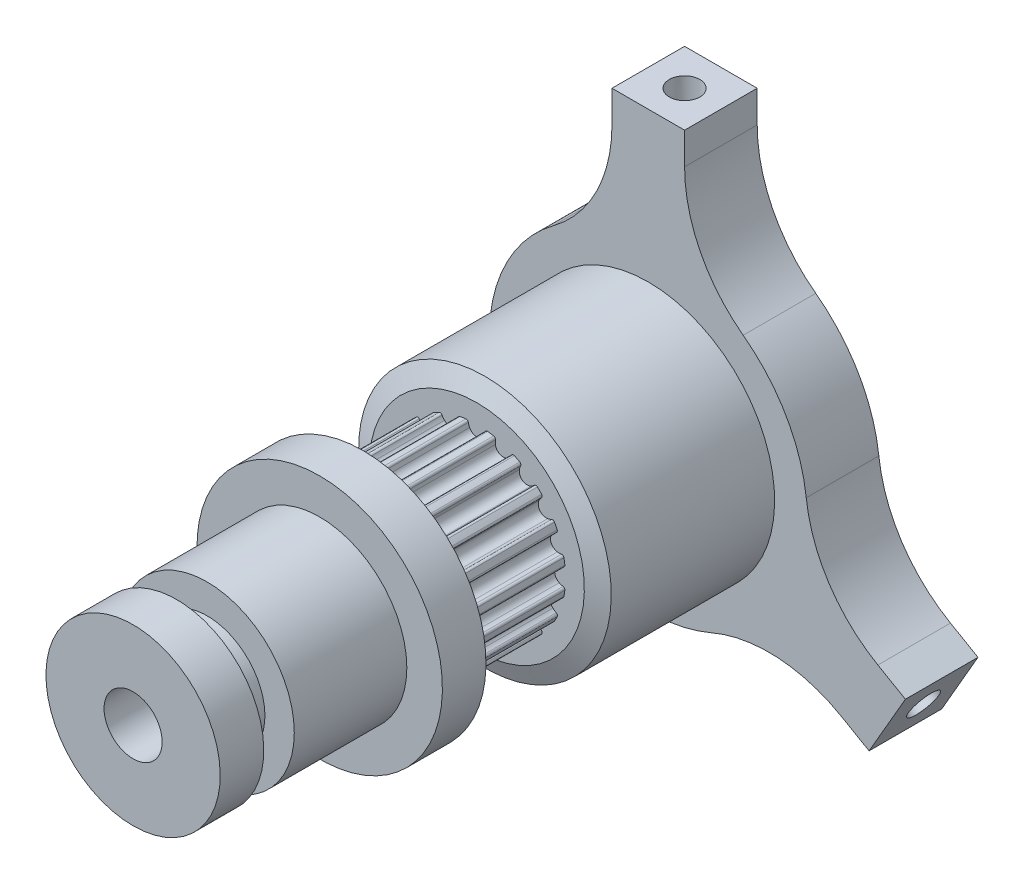
SolidWorks part; units mm, degrees
ref_plane "Front Plane" through (0, 0, 0) normal (0, 0, 1) x (1, 0, 0)
ref_plane "Top Plane" through (0, 0, 0) normal (0, 1, 0) x (1, 0, 0)
ref_plane "Right Plane" through (0, 0, 0) normal (1, 0, 0) x (0, 0, -1)
sketch "Sketch10" plane through (0, 0, 0) normal (0, 0, 1) x (1, 0, 0)
  circle A0 centre (0, 0) radius 2 construction
  dimension "D1" = 4
sketch "Sketch1" plane through (0, 0, 0) normal (0, 0, 1) x (1, 0, 0)
  line L5 (7.9825, -7.4955) -> (15.2045, -11.6651)
  line L6 (10.4825, -3.1653) -> (17.7045, -7.3349)
  line L7 (15.2045, -11.6651) -> (17.7045, -7.3349)
  line L9 (-10.4825, -3.1653) -> (-17.7045, -7.3349)
  line L10 (-7.9825, -7.4955) -> (-15.2045, -11.6651)
  line L11 (-17.7045, -7.3349) -> (-15.2045, -11.6651)
  line L13 (-2.5, 10.6608) -> (-2.5, 19)
  line L14 (2.5, 10.6608) -> (2.5, 19)
  line L15 (-2.5, 19) -> (2.5, 19)
  line L16 (-10.4825, -3.1653) -> (-2.5, 10.6608) construction
  line L17 (2.5, 10.6608) -> (10.4825, -3.1653) construction
  line L18 (-7.9825, -7.4955) -> (7.9825, -7.4955) construction
  line L19 (2.5, 19) -> (17.7045, -7.3349) construction
  line L20 (15.2045, -11.6651) -> (-15.2045, -11.6651) construction
  line L21 (-17.7045, -7.3349) -> (-2.5, 19) construction
  arc A0 (10.4825, -3.1653) -> (2.5, 10.6608) centre (0, 0) ccw
  arc A1 (-2.5, 10.6608) -> (-10.4825, -3.1653) centre (0, 0) ccw
  arc A2 (-7.9825, -7.4955) -> (7.9825, -7.4955) centre (0, 0) ccw
  dimension "D1" = 21.9
  dimension "D2" = 5
  dimension "D3" = 19
extrude "Boss-Extrude1" add sketch "Sketch1" along normal blind 5
sketch "main_revolve_sketch" plane through (0, 0, 0) normal (1, 0, 0) x (0, 0, -1)
  line L0 (-5, 0) -> (-5, 8.7)
  line L1 (-5, 8.7) -> (-16.25, 8.7)
  line L2 (-16.25, 8.7) -> (-16.8068, 7.404)
  line L3 (-16.8068, 7.404) -> (-16.8068, 6.1085)
  line L4 (-16.8068, 6.1085) -> (-24.1768, 6.1085)
  line L5 (-24.1768, 6.1085) -> (-24.1768, 7.404)
  line L6 (-24.1768, 7.404) -> (-24.6263, 8.45)
  line L7 (-24.6263, 8.45) -> (-27.6263, 8.45)
  line L8 (-5, 0) -> (-27.6263, 0) construction
  line L9 (-27.6263, 8.45) -> (-27.6263, 0)
  line L10 (-24.1768, 7.404) -> (-24.7337, 8.7) construction
  line L11 (-20.4918, 6.1085) -> (-20.4918, 0) construction
  line L12 (-5, 10.6608) -> (-5, -3.1653) construction
  line L13 (-5, 0) -> (-27.6263, 0)
  line L14 (-24.7337, 8.7) -> (-16.25, 8.7) construction
  line L15 (-20.4918, 8.7) -> (-20.4918, 6.1085) construction
  dimension "D1" = 17.4
  dimension "D2" = 7.37
  dimension "D3" = 8.38
  dimension "D4" = 12.217
  dimension "D5" = 14.808
  dimension "length_difference" = 11.25
  dimension "D7" = 3
  dimension "D8" = 0.25
revolve "main_revolve" add sketch "main_revolve_sketch" angle 360 about L13
sketch "Sketch11" plane through (0, 0, 27.6263) normal (0, 0, 1) x (1, 0, 0)
  circle A2 centre (0, 0) radius 6
  circle A3 centre (0, 0) radius 6
  dimension "D1" = 4
extrude "Boss-Extrude3" add sketch "Sketch11" along normal blind 7.75
sketch "Sketch13" plane through (0, 0, 0) normal (1, 0, 0) x (0, 0, -1)
  line L0 (-35.3763, 0) -> (-35.3763, 3.9775)
  line L1 (-35.3763, 6) -> (-35.3763, -6) construction
  line L2 (-35.3763, 3.9775) -> (-37.4763, 3.9775)
  line L3 (-37.4763, 3.9775) -> (-37.4763, 6)
  line L4 (-37.4763, 6) -> (-40.4763, 6)
  line L5 (-40.4763, 6) -> (-40.4763, 0)
  line L6 (-40.4763, 0) -> (-35.3763, 0) construction
  line L7 (-27.6263, 6) -> (-35.3763, 6) construction
  line L8 (-35.3763, 0) -> (-40.4763, 0)
  dimension "D1" = 3
  dimension "D2" = 2.1
  dimension "D3" = 7.955
revolve "Revolve2" add sketch "Sketch13" angle 360 about L6
sketch "Sketch2" plane through (0, 19, 0) normal (0, 1, 0) x (1, 0, 0)
  line L0 (0, 0) -> (0, -2.5) construction
  line L1 (0, -2.5) -> (2.5, -2.5) construction
  line L2 (2.5, -5) -> (2.5, 0) construction
  circle A0 centre (0, -2.5) radius 1.05
  dimension "D1" = 2.1
extrude "Cut-Extrude1" cut sketch "Sketch2" against normal blind 10
pattern_circular "CirPattern2" count 3 over 360 about axis through (0, 0, 5) along (0, 0, -1) of "Cut-Extrude1"
draft "Draft4" type of draft neutral plane draft angle 1 faces to draft 1 face at (0, 9, 3.55) neutral plane through (-2.5, 19, 5) neutral plane normal (0, 1, 0) parameters "D1"=1
draft "Draft5" type of draft neutral plane draft angle 1 faces to draft 1 face at (-7.7942, -4.5, 3.55) neutral plane through (-17.7045, -7.3349, 5) neutral plane normal (-0.866, -0.5, 0) parameters "D1"=1
draft "Draft6" type of draft neutral plane draft angle 1 faces to draft 1 face at (7.7942, -4.5, 3.55) neutral plane through (15.2045, -11.6651, 5) neutral plane normal (0.866, -0.5, 0) parameters "D1"=1
sketch "Sketch3" plane through (0, 0, 0) normal (0, 0, -1) x (-1, 0, 0)
  circle A0 centre (0, 0) radius 2
  circle A1 centre (0, 0) radius 2 construction
extrude "Cut-Extrude2" cut sketch "Sketch3" against normal through all
sketch "Sketch7" plane through (0, 0, 16.8068) normal (0, 0, 1) x (1, 0, 0)
  line B0 (0, 0) -> (0, 5.3585) construction
  line B1 (-1.8963, 5.8067) -> (-2.841, 8.6995)
  line B2 (-2.841, 8.6995) -> (2.841, 8.6995)
  line B3 (2.841, 8.6995) -> (1.8963, 5.8067)
  arc B4 (-0.4989, 5.6703) -> (0.4989, 5.6703) centre (0, 5.9135) ccw
  arc B5 (-0.4989, 5.6703) -> (-0.5855, 5.9387) centre (0.4, 6.1085) cw
  arc B6 (-1.8963, 5.8067) -> (-0.7518, 6.0621) centre (0, 0) cw
  arc B7 (-0.5855, 5.9387) -> (-0.7518, 6.0621) centre (-0.7333, 5.9132) ccw
  arc B8 (1.8963, 5.8067) -> (0.7518, 6.0621) centre (0, 0) ccw
  arc B9 (0.5855, 5.9387) -> (0.7518, 6.0621) centre (0.7333, 5.9132) cw
  arc B10 (0.4989, 5.6703) -> (0.5855, 5.9387) centre (-0.4, 6.1085) ccw
sketch_block_instance "Block-Gt Timing Belt Pulley Groove-1"
sketch_block "Block-Gt Timing Belt Pulley Groove" parameters "D1"=12.725, "D2"=17.399, "D6"=0.555, "D7"=1, "D9"=0.15, "D3"=9.6972, "D4"=4.8486, "D5"=2, "D8"=0.254, "D10"=0.4, "D11"=0.75
extrude "Cut-Extrude3" cut sketch "Sketch7" along normal up to surface (7.37 mm away) up to face at (0, 7.404, 24.1768)
pattern_circular "CirPattern4" count 20 over 360 about axis through (0, 0, 40.4763) along (0, 0, -1) of "Cut-Extrude3"
fillet "Fillet1" radius 10 6 edges at (2.5, 10.6608, 2.5) (10.4825, -3.1653, 2.5) (7.9825, -7.4955, 2.5) (-7.9825, -7.4955, 2.5) (-10.4825, -3.1653, 2.5) (-2.5, 10.6608, 2.5)
ref_plane "Plane1" through (0, 0, 20.4918) normal (0, 0, 1) x (1, 0, 0)
